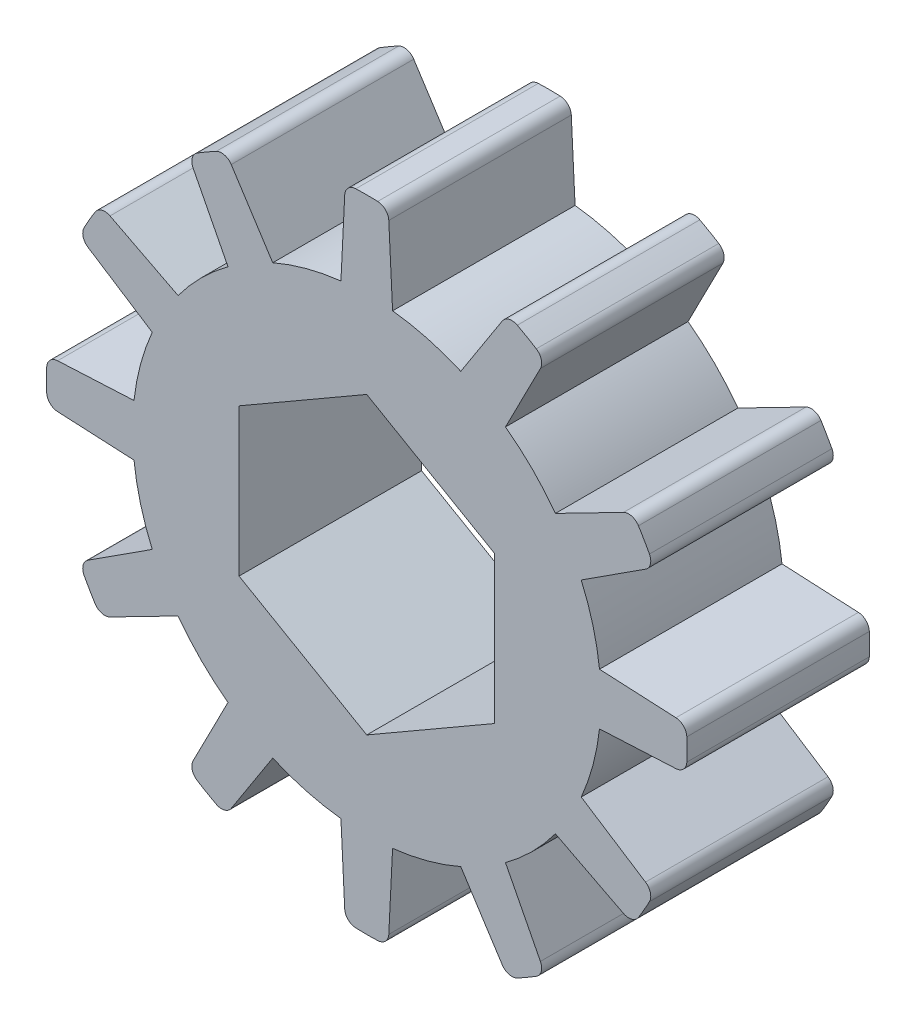
SolidWorks part; units mm, degrees
material "ABS"
ref_plane "Alzado" through (0, 0, 0) normal (0, 0, 1) x (1, 0, 0)
ref_plane "Planta" through (0, 0, 0) normal (0, 1, 0) x (1, 0, 0)
ref_plane "Vista lateral" through (0, 0, 0) normal (1, 0, 0) x (0, 0, -1)
sketch "Croquis1" plane through (0, 0, 0) normal (0, 0, 1) x (1, 0, 0)
  line L0 (0, 0) -> (0, 4.6049) construction
  line L1 (0.375, 5.5679) -> (0.45, 4.0556)
  line L2 (-0.375, 5.5679) -> (-0.45, 4.0556)
  line L3 (2.4592, 5.0094) -> (1.6381, 3.7373)
  line L4 (3.1087, 4.6344) -> (2.4175, 3.2873)
  line L5 (4.6344, 3.1087) -> (3.2873, 2.4175)
  line L6 (5.0094, 2.4592) -> (3.7373, 1.6381)
  line L7 (5.5679, 0.375) -> (4.0556, 0.45)
  line L8 (5.5679, -0.375) -> (4.0556, -0.45)
  line L9 (5.0094, -2.4592) -> (3.7373, -1.6381)
  line L10 (4.6344, -3.1087) -> (3.2873, -2.4175)
  line L11 (3.1087, -4.6344) -> (2.4175, -3.2873)
  line L12 (2.4592, -5.0094) -> (1.6381, -3.7373)
  line L13 (0.375, -5.5679) -> (0.45, -4.0556)
  line L14 (-0.375, -5.5679) -> (-0.45, -4.0556)
  line L15 (-2.4592, -5.0094) -> (-1.6381, -3.7373)
  line L16 (-3.1087, -4.6344) -> (-2.4175, -3.2873)
  line L17 (-4.6344, -3.1087) -> (-3.2873, -2.4175)
  line L18 (-5.0094, -2.4592) -> (-3.7373, -1.6381)
  line L19 (-5.5679, -0.375) -> (-4.0556, -0.45)
  line L20 (-5.5679, 0.375) -> (-4.0556, 0.45)
  line L21 (-5.0094, 2.4592) -> (-3.7373, 1.6381)
  line L22 (-4.6344, 3.1087) -> (-3.2873, 2.4175)
  line L23 (-3.1087, 4.6344) -> (-2.4175, 3.2873)
  line L24 (-2.4592, 5.0094) -> (-1.6381, 3.7373)
  circle A0 centre (0, 0) radius 0.5
  arc A1 (1.6381, 3.7373) -> (0.45, 4.0556) centre (0, 0) ccw
  arc A2 (3.1087, 4.6344) -> (2.4592, 5.0094) centre (0, 0) ccw
  arc A3 (5.0094, 2.4592) -> (4.6344, 3.1087) centre (0, 0) ccw
  arc A4 (5.5679, -0.375) -> (5.5679, 0.375) centre (0, 0) ccw
  arc A5 (4.6344, -3.1087) -> (5.0094, -2.4592) centre (0, 0) ccw
  arc A6 (2.4592, -5.0094) -> (3.1087, -4.6344) centre (0, 0) ccw
  arc A7 (-0.375, -5.5679) -> (0.375, -5.5679) centre (0, 0) ccw
  arc A8 (-3.1087, -4.6344) -> (-2.4592, -5.0094) centre (0, 0) ccw
  arc A9 (-5.0094, -2.4592) -> (-4.6344, -3.1087) centre (0, 0) ccw
  arc A10 (-5.5679, 0.375) -> (-5.5679, -0.375) centre (0, 0) ccw
  arc A11 (-4.6344, 3.1087) -> (-5.0094, 2.4592) centre (0, 0) ccw
  arc A12 (-2.4592, 5.0094) -> (-3.1087, 4.6344) centre (0, 0) ccw
  arc A13 (0.375, 5.5679) -> (-0.375, 5.5679) centre (0, 0) ccw
  arc A14 (3.2873, 2.4175) -> (2.4175, 3.2873) centre (0, 0) ccw
  arc A15 (4.0556, 0.45) -> (3.7373, 1.6381) centre (0, 0) ccw
  arc A16 (3.7373, -1.6381) -> (4.0556, -0.45) centre (0, 0) ccw
  arc A17 (2.4175, -3.2873) -> (3.2873, -2.4175) centre (0, 0) ccw
  arc A18 (0.45, -4.0556) -> (1.6381, -3.7373) centre (0, 0) ccw
  arc A19 (-1.6381, -3.7373) -> (-0.45, -4.0556) centre (0, 0) ccw
  arc A20 (-3.2873, -2.4175) -> (-2.4175, -3.2873) centre (0, 0) ccw
  arc A21 (-4.0556, -0.45) -> (-3.7373, -1.6381) centre (0, 0) ccw
  arc A22 (-3.7373, 1.6381) -> (-4.0556, 0.45) centre (0, 0) ccw
  arc A23 (-2.4175, 3.2873) -> (-3.2873, 2.4175) centre (0, 0) ccw
  arc A24 (-0.45, 4.0556) -> (-1.6381, 3.7373) centre (0, 0) ccw
  dimension "D1" = 0.9
  dimension "D2" = 1
  dimension "D4" = 1.5
  dimension "D3" = 0.75
  dimension "D6" = 1.23
  dimension "D5" = 12
extrude "Saliente-Extruir1" add sketch "Croquis1" along normal blind 3.18
sketch "Croquis10" plane through (0, 0, 0) normal (0, 0, -1) x (-1, 0, 0)
  line L1 (0, -2.5692) -> (2.225, -1.2846)
  line L2 (2.225, -1.2846) -> (2.225, 1.2846)
  line L3 (2.225, 1.2846) -> (0, 2.5692)
  line L4 (0, 2.5692) -> (-2.225, 1.2846)
  line L5 (-2.225, 1.2846) -> (-2.225, -1.2846)
  line L6 (-2.225, -1.2846) -> (0, -2.5692)
  circle A0 centre (0, 0) radius 2.225 construction
  dimension "D1" = 4.45
extrude "Cortar-Extruir3" cut sketch "Croquis10" against normal through all
fillet "Redondeo1" radius 0.2 24 edges at (5.5679, -0.375, 1.59) (-2.4592, -5.0094, 1.59) (-3.1087, -4.6344, 1.59) (0.375, -5.5679, 1.59) (-0.375, -5.5679, 1.59) (3.1087, -4.6344, 1.59) (2.4592, -5.0094, 1.59) (5.0094, -2.4592, 1.59) (4.6344, -3.1087, 1.59) (-4.6344, -3.1087, 1.59) (-5.0094, -2.4592, 1.59) (-5.5679, -0.375, 1.59) (-5.5679, 0.375, 1.59) (-5.0094, 2.4592, 1.59) (-4.6344, 3.1087, 1.59) (-3.1087, 4.6344, 1.59) (-2.4592, 5.0094, 1.59) (5.5679, 0.375, 1.59) (5.0094, 2.4592, 1.59) (4.6344, 3.1087, 1.59) (3.1087, 4.6344, 1.59) (2.4592, 5.0094, 1.59) (0.375, 5.5679, 1.59) (-0.375, 5.5679, 1.59)
